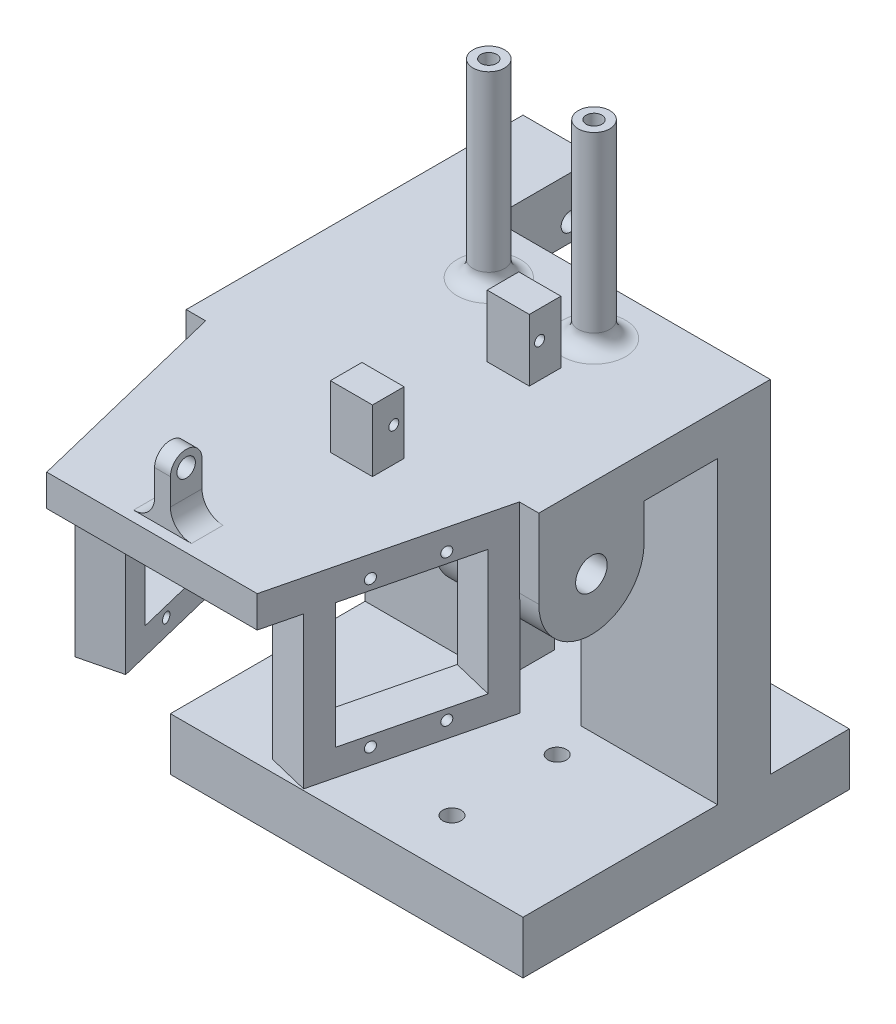
SolidWorks part; units mm, degrees
ref_plane "前视基准面" through (0, 0, 0) normal (0, 0, 1) x (1, 0, 0)
ref_plane "上视基准面" through (0, 0, 0) normal (0, 1, 0) x (1, 0, 0)
ref_plane "右视基准面" through (0, 0, 0) normal (1, 0, 0) x (0, 0, -1)
sketch "草图1" plane through (0, 0, 0) normal (0, 1, 0) x (1, 0, 0)
  line L1 (-33.5, 31) -> (33.5, 31)
  line L2 (-33.5, 31) -> (-33.5, -31)
  line L3 (-33.5, -31) -> (33.5, -31)
  line L4 (33.5, 31) -> (33.5, -31)
  line L5 (-33.5, 31) -> (33.5, -31) construction
  line L6 (-33.5, -31) -> (33.5, 31) construction
  point P0 (0, 0)
  dimension "D1" = 62
  dimension "D2" = 67
extrude "凸台-拉伸1" add sketch "草图1" along normal blind 10
sketch "草图3" plane through (0, 10, 0) normal (0, 1, 0) x (1, 0, 0)
  line L0 (-33.5, 31) -> (-33.5, -31) construction
  line L1 (-33.5, 36) -> (-19.5, 36)
  line L2 (-33.5, 36) -> (-33.5, 16)
  line L3 (-33.5, 16) -> (-19.5, 16)
  line L4 (-19.5, 36) -> (-19.5, 16)
  line L5 (33.5, 31) -> (-33.5, 31) construction
  dimension "D1" = 20
  dimension "D2" = 5
  dimension "D3" = 19.5
extrude "凸台-拉伸2" add sketch "草图3" along normal blind 12.5
sketch "草图4" plane through (-33.5, 0, 0) normal (-1, 0, 0) x (0, 0, 1)
  line L1 (-16, 10) -> (-6, 10)
  line L2 (-16, 10) -> (-16, 75)
  line L3 (-16, 75) -> (-6, 75)
  line L4 (-6, 10) -> (-6, 75)
  dimension "D1" = 10
  dimension "D2" = 65
extrude "凸台-拉伸3" add sketch "草图4" against normal blind 67
sketch "草图5" plane through (0, 75, 0) normal (0, 1, 0) x (1, 0, 0)
  line L0 (33.5, -31) -> (33.5, 6) construction
  line L1 (-33.5, 16) -> (33.5, 16)
  line L2 (-33.5, 16) -> (-33.5, -28)
  line L3 (-33.5, -28) -> (33.5, -28)
  line L4 (33.5, 16) -> (33.5, -28)
  dimension "D1" = 44
extrude "凸台-拉伸4" add sketch "草图5" against normal blind 8
sketch "草图6" plane through (33.5, 0, 0) normal (1, 0, 0) x (0, 0, -1)
  line L0 (6, 10) -> (6, 67) construction
  line L1 (-28, 75) -> (16, 75) construction
  line L2 (-28, 60) -> (-28, 67)
  line L3 (-28, 67) -> (6, 67) construction
  line L5 (-28, 67) -> (-8, 67)
  line L6 (-8, 67) -> (-8, 60)
  arc A0 (-28, 60) -> (-8, 60) centre (-18, 60) ccw
  dimension "D1" = 24
  dimension "D2" = 15
  dimension "D3" = 20
extrude "凸台-拉伸5" add sketch "草图6" against normal blind 20
sketch "草图7" plane through (33.5, 0, 0) normal (1, 0, 0) x (0, 0, -1)
  line L0 (-28, 60) -> (-28, 70.0002)
  line L1 (-28, 60) -> (-28, 75) construction
  line L2 (-28, 70.0002) -> (-8, 70.0002)
  line L3 (-8, 70.0002) -> (-8, 60)
  arc A0 (-28, 60) -> (-8, 60) centre (-18, 60) ccw construction
  arc A1 (-28, 60) -> (-8, 60) centre (-18, 60) ccw
extrude "切除-拉伸1" cut sketch "草图7" against normal blind 8 from offset 6 offset against normal yes
sketch "草图8" plane through (0, 75, 0) normal (0, 1, 0) x (1, 0, 0)
  line L0 (0, -68) -> (20, -68)
  line L2 (20, -68) -> (29.8044, -28)
  line L3 (29.8044, -28) -> (0, -28)
  line L4 (0, -28) -> (0, -68)
  line L5 (-33.5, -28) -> (33.5, -28) construction
  dimension "D1" = 20
  dimension "D2" = 40
extrude "凸台-拉伸6" add sketch "草图8" against normal blind 6
sketch "草图9" plane through (33.5, 0, 0) normal (1, 0, 0) x (0, 0, -1)
  circle A0 centre (-18, 60) radius 3
  dimension "D1" = 6
extrude "切除-拉伸2" cut sketch "草图9" against normal blind 23
sketch "草图10" plane through (34.5894, 0, 8.4782) normal (0.9712, 0, 0.2381) x (0.2381, 0, -0.9712)
  line L1 (-49, 75) -> (-20, 75)
  line L4 (-20, 75) -> (-20, 40.2)
  line L5 (-20, 40.2) -> (-48, 40.2)
  line L9 (-49, 45.2) -> (-25, 45.2)
  line L10 (-25, 45.2) -> (-25, 69)
  line L11 (-25, 69) -> (-49, 69)
  line L12 (-61.2837, 75) -> (-20.0997, 75) construction
  line L14 (-49, 75) -> (-54, 75)
  line L15 (-61.2837, 75) -> (-20.0997, 75) construction
  line L16 (-49, 69) -> (-49, 45.2)
  line L17 (-48, 40.2) -> (-54, 40.2)
  line L18 (-54, 75) -> (-54, 40.2)
  dimension "D1" = 5
  dimension "D2" = 5
  dimension "D3" = 29
  dimension "D4" = 20
  dimension "D5" = 24
  dimension "D6" = 28
  dimension "D7" = 5
  dimension "D8" = 6
  dimension "D9" = 23.8
extrude "凸台-拉伸7" add sketch "草图10" against normal blind 8
sketch "草图12" plane through (0, 75, 0) normal (0, 1, 0) x (1, 0, 0)
  line L1 (-33.5, 36) -> (-19.5, 36)
  line L2 (-33.5, 36) -> (-33.5, 16)
  line L3 (-33.5, 16) -> (-19.5, 16)
  line L4 (-19.5, 36) -> (-19.5, 16)
extrude "凸台-拉伸8" add sketch "草图12" against normal blind 11.5
sketch "草图13" plane through (26.8194, 0, 6.5737) normal (-0.9712, 0, -0.2381) x (-0.2381, 0, 0.9712)
  line L0 (61.2837, 69) -> (54, 69) construction
  line L7 (25, 69) -> (25, 45.2) construction
  line L8 (25, 45.2) -> (49, 45.2) construction
  circle A0 centre (43.5, 70.95) radius 0.95
  circle A1 centre (31.5, 70.95) radius 0.95
  circle A2 centre (31.5, 43.25) radius 0.95
  circle A3 centre (43.5, 43.25) radius 0.95
  dimension "D2" = 6.5
  dimension "D3" = 1.95
  dimension "D4" = 1.95
  dimension "D5" = 12
  dimension "D6" = 1.9
  dimension "D7" = 1.9
  dimension "D13" = 1.9
  dimension "D14" = 1.9
extrude "切除-拉伸4" cut sketch "草图13" against normal up to surface (8 mm away) up to face at (25.3409, 60.8763, 46.2102)
sketch "草图14" plane through (0, 75, 0) normal (0, 1, 0) x (1, 0, 0)
  line L0 (33.5, 6) -> (-33.5, 6) construction
  line L1 (3.7, -2) -> (11.7, -2)
  line L2 (3.7, -2) -> (3.7, -8)
  line L3 (3.7, -8) -> (11.7, -8)
  line L4 (11.7, -2) -> (11.7, -8)
  line L5 (11.7, -31.8) -> (11.7, -37.8)
  line L6 (3.7, -37.8) -> (11.7, -37.8)
  line L7 (3.7, -31.8) -> (3.7, -37.8)
  line L8 (3.7, -31.8) -> (11.7, -31.8)
  dimension "D1" = 11.7
  dimension "D2" = 3.7
  dimension "D3" = 6
  dimension "D4" = 14
  dimension "D5" = 6
  dimension "D6" = 8
  dimension "D7" = 23.8
extrude "凸台-拉伸9" add sketch "草图14" along normal blind 11.8
sketch "草图15" plane through (3.7, 0, 0) normal (-1, 0, 0) x (0, 0, 1)
  line L0 (8, 86.8) -> (8, 75) construction
  line L1 (28, 75) -> (-36, 75) construction
  line L2 (31.8, 75) -> (37.8, 75) construction
  line L3 (31.8, 86.8) -> (31.8, 75) construction
  circle A0 centre (33.75, 81.5) radius 0.95
  circle A1 centre (6.05, 81.5) radius 0.95
  dimension "D1" = 1.95
  dimension "D2" = 1.95
  dimension "D3" = 1.9
  dimension "D4" = 1.9
  dimension "D5" = 6.5
  dimension "D6" = 6.5
extrude "切除-拉伸5" cut sketch "草图15" against normal blind 11.8
sketch "草图16" plane through (0, 75, 0) normal (0, 1, 0) x (1, 0, 0)
  line L1 (-1.5, -60) -> (1.5, -60)
  line L2 (-1.5, -60) -> (-1.5, -66)
  line L3 (-1.5, -66) -> (1.5, -66)
  line L4 (1.5, -60) -> (1.5, -66)
  point P4 (0, -66)
  dimension "D2" = 6
  dimension "D3" = 3
  dimension "D4" = 60
extrude "凸台-拉伸10" add sketch "草图16" along normal blind 12
fillet "圆角1" 2 edges at (0, 87, 66) (0, 87, 60) type full round first side face at (0, 79.8, 66) second side face at (0, 79.8, 60) middle face at (0, 87, 63)
sketch "草图17" plane through (-1.5, 0, 0) normal (-1, 0, 0) x (0, 0, 1)
  circle A0 centre (63, 84) radius 1.75
  arc A1 (66, 84) -> (60, 84) centre (63, 84) ccw construction
  dimension "D1" = 3.5
extrude "切除-拉伸6" cut sketch "草图17" against normal blind 7
sketch "草图18" plane through (0, 75, 0) normal (0, 1, 0) x (1, 0, 0)
  line L0 (33.5, 16) -> (-19.5, 16) construction
  circle A0 centre (10, 6) radius 3
  dimension "D1" = 6
  dimension "D2" = 10
  dimension "D3" = 10
extrude "凸台-拉伸11" add sketch "草图18" along normal blind 36
fillet "圆角2" radius 3 1 edges at (10, 75, -3)
mirror "镜向1" about plane through (0, 0, 0) normal (1, 0, 0) of "圆角2", "凸台-拉伸11", "切除-拉伸4", "凸台-拉伸7", "切除-拉伸2", "凸台-拉伸6", "切除-拉伸1", "凸台-拉伸5"
sketch "草图20" plane through (-33.5, 0, 0) normal (-1, 0, 0) x (0, 0, 1)
  line L0 (-36, 63.5) -> (-16, 63.5) construction
  line L1 (-36, 63.5) -> (-36, 75) construction
  circle A0 centre (-31, 67) radius 1.75
  circle A1 centre (-21, 67) radius 1.75
  circle A2 centre (-31, 19) radius 1.75
  circle A3 centre (-21, 19) radius 1.75
  dimension "D1" = 3.5
  dimension "D2" = 10
  dimension "D3" = 48
  dimension "D4" = 3.5
  dimension "D5" = 5
extrude "切除-拉伸7" cut sketch "草图20" against normal blind 35
sketch "草图21" plane through (0, 0, -16) normal (0, 0, -1) x (-1, 0, 0)
  line L1 (-7.5, 65) -> (7.5, 65)
  line L2 (-7.5, 65) -> (-7.5, 10)
  line L3 (-7.5, 10) -> (7.5, 10)
  line L4 (7.5, 65) -> (7.5, 10)
  line L5 (-33.5, 10) -> (19.5, 10) construction
  point P8 (0, 10)
  dimension "D1" = 15
  dimension "D2" = 55
extrude "切除-拉伸8" cut sketch "草图21" against normal blind 35
sketch "草图24" plane through (0, 10, 0) normal (0, 1, 0) x (1, 0, 0)
  line L0 (-33.5, -31) -> (33.5, -31) construction
  circle A0 centre (-10, -21) radius 1.75
  circle A1 centre (10, -21) radius 1.75
  circle A2 centre (-10, -1) radius 1.75
  circle A3 centre (10, -1) radius 1.75
  point P10 (0, -31)
  dimension "D1" = 20
  dimension "D2" = 20
  dimension "D5" = 10
  dimension "D6" = 3.5
  dimension "D7" = 10
  dimension "D3" = 20
  dimension "D4" = 20
extrude "切除-拉伸11" cut sketch "草图24" against normal blind 18
sketch "草图25" plane through (0, 111, 0) normal (0, 1, 0) x (1, 0, 0)
  circle A0 centre (10, 6) radius 1.5
  circle A1 centre (-10, 6) radius 1.5
  dimension "D1" = 3
  dimension "D2" = 3
extrude "切除-拉伸12" cut sketch "草图25" against normal blind 10
fillet "圆角3" radius 4 2 edges at (-1.5, 75, 63) (1.5, 75, 63)
sketch "草图26" plane through (0, 69, 0) normal (0, -1, 0) x (1, 0, 0)
  line L0 (-20, 68) -> (20, 68) construction
  line L1 (-5, 63.9) -> (5.1, 63.9)
  line L2 (-5, 63.9) -> (-5, 60.15)
  line L3 (-5, 60.15) -> (5.1, 60.15)
  line L4 (5.1, 63.9) -> (5.1, 60.15)
  line L5 (-5, 63.9) -> (5.1, 60.15) construction
  line L6 (-5, 60.15) -> (5.1, 63.9) construction
  line L7 (-33.5, -31) -> (-33.5, 31) construction
  point P0 (0.05, 62.025)
  dimension "D1" = 3.75
  dimension "D2" = 10.1
  dimension "D3" = 4.1
  dimension "D4" = 28.5
extrude "凸台-拉伸12" add sketch "草图26" along normal blind 1
sketch "草图27" plane through (0, 68, 0) normal (0, -1, 0) x (1, 0, 0)
  line L0 (-20, 68) -> (20, 68) construction
  line L1 (-33.5, -31) -> (-33.5, 31) construction
  circle A0 centre (0, 62) radius 1.4
  point P6 (-18.5332, 72.5897)
  dimension "D1" = 2.8
  dimension "D2" = 6
  dimension "D3" = 33.5
extrude "切除-拉伸13" cut sketch "草图27" against normal blind 4
